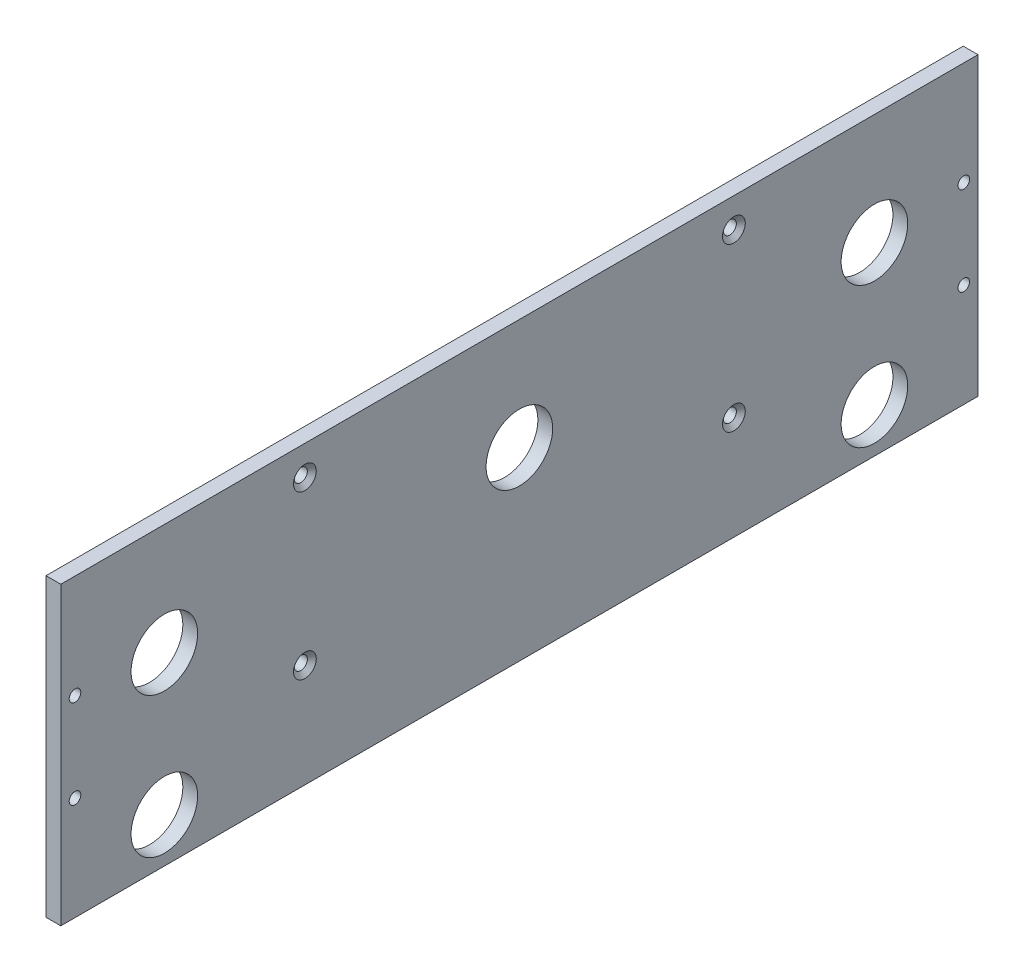
SolidWorks part; units mm, degrees
material "6061-T6 (SS)"
ref_plane "Front Plane" through (0, 0, 0) normal (0, 0, 1) x (1, 0, 0)
ref_plane "Top Plane" through (0, 0, 0) normal (0, 1, 0) x (1, 0, 0)
ref_plane "Right Plane" through (0, 0, 0) normal (1, 0, 0) x (0, 0, -1)
sketch "Sketch1" plane through (0, 0, 0) normal (1, 0, 0) x (0, 0, -1)
  line L1 (-196.85, 63.5) -> (196.85, 63.5)
  line L2 (-196.85, 63.5) -> (-196.85, -63.5)
  line L3 (-196.85, -63.5) -> (196.85, -63.5)
  line L4 (196.85, 63.5) -> (196.85, -63.5)
  line L5 (-196.85, 63.5) -> (196.85, -63.5) construction
  line L6 (-196.85, -63.5) -> (196.85, 63.5) construction
  point P0 (0, 0)
  dimension "D1" = 127
  dimension "D2" = 393.7
extrude "Boss-Extrude1" add sketch "Sketch1" along normal blind 6.35
sketch "Sketch2" plane through (6.35, 0, 0) normal (1, 0, 0) x (0, 0, -1)
  line L0 (-196.85, -63.5) -> (196.85, -63.5) construction
  line L1 (-152.4, 15.875) -> (0, 15.875) construction
  line L2 (-76.2, -34.925) -> (-76.2, 15.875) construction
  line L3 (0, 15.875) -> (152.4, 15.875) construction
  line L4 (76.2, -34.925) -> (76.2, 15.875) construction
  line L5 (196.85, 63.5) -> (-196.85, 63.5) construction
  line L6 (65.278, 53.34) -> (-56.642, 53.34) construction
  line L7 (65.278, 53.34) -> (65.278, -13.97) construction
  line L8 (65.278, -13.97) -> (-56.642, -13.97) construction
  line L9 (-56.642, 53.34) -> (-56.642, -13.97) construction
  line L10 (-196.85, -63.5) -> (196.85, -63.5) construction
  circle A0 centre (0, 15.875) radius 14.2875
  circle A1 centre (-152.4, 15.875) radius 14.2875
  circle A2 centre (152.4, 15.875) radius 14.2875
  circle A3 centre (-152.4, 15.875) radius 38.1 construction
  circle A4 centre (0, 15.875) radius 38.1 construction
  circle A5 centre (152.4, 15.875) radius 38.1 construction
  circle A6 centre (-76.2, -34.925) radius 6.35 construction
  circle A7 centre (76.2, -34.925) radius 6.35 construction
  circle A8 centre (-76.2, 9.525) radius 6.35 construction
  circle A9 centre (76.2, 9.525) radius 6.35 construction
  circle A11 centre (-152.4, -44.45) radius 14.2875
  circle A12 centre (152.4, -44.45) radius 14.2875
  point P11 (0, 0)
  dimension "D1" = 28.575
  dimension "D5" = 76.2
  dimension "D7" = 12.7
  dimension "D14" = 28.575
  dimension "D15" = 19.05
  dimension "D17" = 28.575
  dimension "D2" = 79.375
  dimension "D3" = 152.4
  dimension "D4" = 152.4
  dimension "D6" = 0
  dimension "D8" = 28.575
  dimension "D9" = 44.45
  dimension "D10" = 56.642
  dimension "D11" = 121.92
  dimension "D12" = 10.16
  dimension "D13" = 49.53
  dimension "D16" = 152.4
  dimension "D18" = 19.05
  dimension "D19" = 152.4
extrude "Cut-Extrude1" cut sketch "Sketch2" against normal through all
sketch "Sketch3" plane through (6.35, 0, 0) normal (1, 0, 0) x (0, 0, -1)
  line L0 (-190.754, 19.05) -> (-190.754, -19.05) construction
  line L1 (-196.85, 63.5) -> (-196.85, -63.5) construction
  point P2 (-190.754, 0)
  point P3 (-196.85, 0)
  dimension "D1" = 38.1
  dimension "D2" = 6.096
hole_wizard "#10 Clearance Hole1" positions "Sketch4" profile "Sketch6" hole size "#10" standard "ANSI Inch" end condition through all
sketch "Sketch4" plane through (6.35, 0, 0) normal (1, 0, 0) x (0, 0, -1)
  line L3 (196.85, -63.5) -> (196.85, 63.5) construction
  point P0 (-190.754, 19.05)
  point P3 (-190.754, -19.05)
  point P8 (190.754, 19.05)
  point P10 (190.754, -19.05)
  dimension "D1" = 6.096
  dimension "D2" = 6.096
sketch "Sketch6" plane through (6.35, 19.05, 190.754) normal (0, 1, 0) x (0, 0, -1)
  line L0 (0, 0) -> (0, 6.35)
  line L1 (0, 6.35) -> (2.4892, 6.35)
  line L2 (2.4892, 6.35) -> (2.4892, 0)
  line L5 (2.4892, 0) -> (0, 0)
  line L11 (0, -6.35) -> (0, 107.95) construction
  dimension "Thru Hole Dia." = 4.9784
  dimension "Thru Hole Depth" = 6.35
hole_wizard "CSK for #10 Flat Head Machine Screw (100)1" positions "Sketch7" profile "Sketch8" countersink size "#10" standard "ANSI Inch" end condition through all
sketch "Sketch7" plane through (6.35, 0, 0) normal (1, 0, 0) x (0, 0, -1)
  line L1 (196.85, 63.5) -> (-196.85, 63.5) construction
  point P15 (-92.075, 50.8)
  point P17 (92.075, 50.8)
  point P19 (-92.075, -19.05)
  point P21 (92.075, -19.05)
  dimension "D1" = 12.7
  dimension "D2" = 12.7
  dimension "D3" = 69.85
  dimension "D4" = 69.85
sketch "Sketch8" plane through (6.35, 50.8, 92.075) normal (0, 1, 0) x (0, 0, -1)
  line L0 (0, 0) -> (0, 6.35)
  line L1 (0, 6.35) -> (2.8067, 6.35)
  line L2 (2.8067, 6.35) -> (2.8067, 1.7477)
  line L3 (2.8067, 1.7477) -> (4.8895, 0)
  line L5 (4.8895, 0) -> (0, 0)
  line L6 (-2.8067, 1.7477) -> (-4.8895, 0) construction
  line L11 (0, -6.35) -> (0, 107.95) construction
  dimension "Thru Hole Dia." = 5.6134
  dimension "Thru Hole Depth" = 6.35
  dimension "Near C'Sink Dia." = 9.779
  dimension "Near C'Sink Angle" = 100
